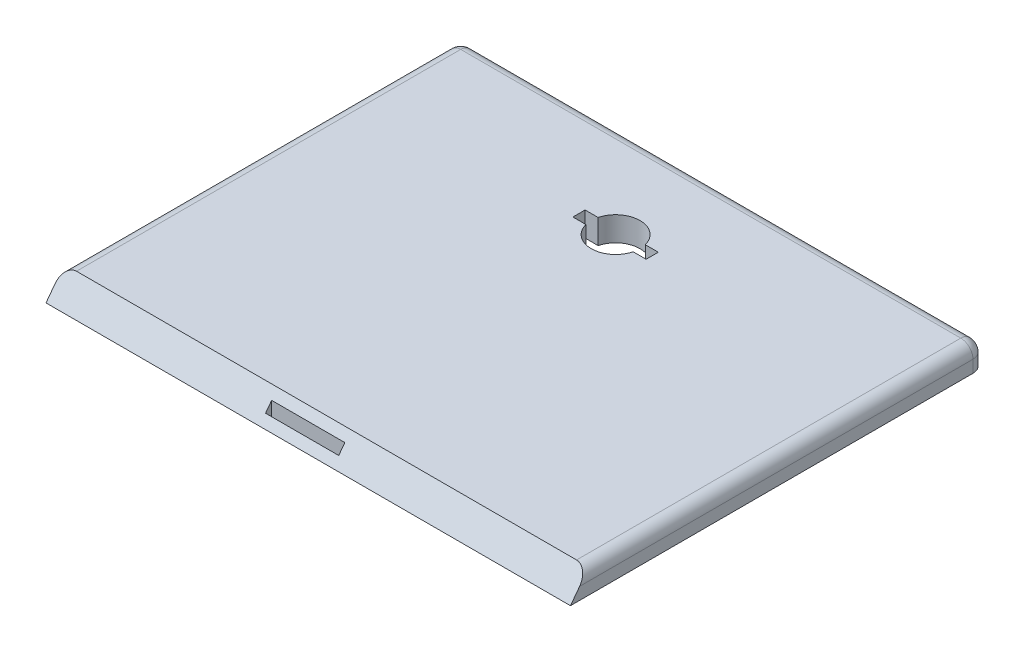
SolidWorks part; units mm, degrees
ref_plane "Ebene vorne" through (0, 0, 0) normal (0, 0, 1) x (1, 0, 0)
ref_plane "Ebene oben" through (0, 0, 0) normal (0, 1, 0) x (1, 0, 0)
ref_plane "Ebene rechts" through (0, 0, 0) normal (1, 0, 0) x (0, 0, -1)
sketch "Skizze1" plane through (0, 0, 0) normal (0, 1, 0) x (1, 0, 0)
  line L1 (-10.75, -8.5) -> (10.75, -8.5)
  line L2 (-10.75, -8.5) -> (-10.75, 8.5)
  line L3 (-10.75, 8.5) -> (10.75, 8.5)
  line L4 (10.75, -8.5) -> (10.75, 8.5)
  line L5 (-10.75, -8.5) -> (10.75, 8.5) construction
  line L6 (-10.75, 8.5) -> (10.75, -8.5) construction
  point P0 (0, 0)
  dimension "D1" = 17
  dimension "D2" = 21.5
extrude "Aufsatz-Linear austragen1" add sketch "Skizze1" along normal blind 1
fillet "Verrundung1" radius 0.5 3 edges at (10.75, 1, 0) (0, 1, -8.5) (-10.75, 1, 0)
sketch "Skizze2" plane through (-10.75, 0, 0) normal (-1, 0, 0) x (0, 0, 1)
  line L0 (8.5, 0) -> (7.75, 1)
  line L1 (-8, 1) -> (8.5, 1) construction
  line L2 (7.75, 1) -> (8.5, 1)
  line L3 (8.5, 1) -> (8.5, 0)
  dimension "D1" = 0.75
extrude "Schnitt-Linear austragen1" cut sketch "Skizze2" against normal up to surface (21.5 mm away) up to face at (10.75, 0.25, 0)
sketch "Skizze4" plane through (0, 1, 0) normal (0, 1, 0) x (1, 0, 0)
  line L6 (10.25, -7.75) -> (-10.25, -7.75) construction
  line L7 (-2, -8.25) -> (1, -8.25)
  line L8 (-2, -8.25) -> (-2, -8)
  line L9 (-2, -8) -> (1, -8)
  line L10 (1, -8.25) -> (1, -8)
  line L11 (-2, -8.25) -> (1, -8) construction
  line L12 (-2, -8) -> (1, -8.25) construction
  line L13 (-10.75, -8.125) -> (-10.75, -8.5) construction
  point P0 (-0.5, -8.125)
  dimension "D1" = 0.25
  dimension "D2" = 0.25
  dimension "D3" = 3
  dimension "D4" = 10.25
extrude "Schnitt-Linear austragen2" cut sketch "Skizze4" against normal up to surface (1 mm away) up to face at (0, 0, 0)
fillet "Verrundung2" radius 0.5 4 edges at (10.6036, 0.8536, -8.3536) (-10.6036, 0.8536, -8.3536) (10.75, 0.25, -8.5) (-10.75, 0.25, -8.5)
sketch "Skizze5" plane through (0, 1, 0) normal (0, 1, 0) x (1, 0, 0)
  line L0 (-10.75, 8) -> (-10.75, -8.5) construction
  line L1 (-2, 4.35) -> (1, 4.35)
  line L2 (-2, 4.35) -> (-2, 4.85)
  line L3 (-2, 4.85) -> (1, 4.85)
  line L4 (1, 4.35) -> (1, 4.85)
  line L5 (-2, 4.35) -> (1, 4.85) construction
  line L6 (-2, 4.85) -> (1, 4.35) construction
  line L7 (-10.25, 8.5) -> (10.25, 8.5) construction
  circle A0 centre (-0.5, 4.6) radius 1
  dimension "D2" = 2
  dimension "D1" = 3
  dimension "D3" = 0.5
  dimension "D4" = 10.25
  dimension "D5" = 3.9
extrude "Schnitt-Linear austragen3" cut sketch "Skizze5" against normal up to surface (1 mm away) contours A0 L3 L2 L1 | L3 A0 | L1 A0 L3 | L1 A0 | A0 L1 L4 L3 region at (-1.7447, 1, -4.6) region at (-0.5, 1, -4.6) region at (-0.5, 1, -4.0376) region at (0.7447, 1, -4.6) region at (-0.5, 1, -5.1624) up to face at (-0.5, 0, 8.125)
